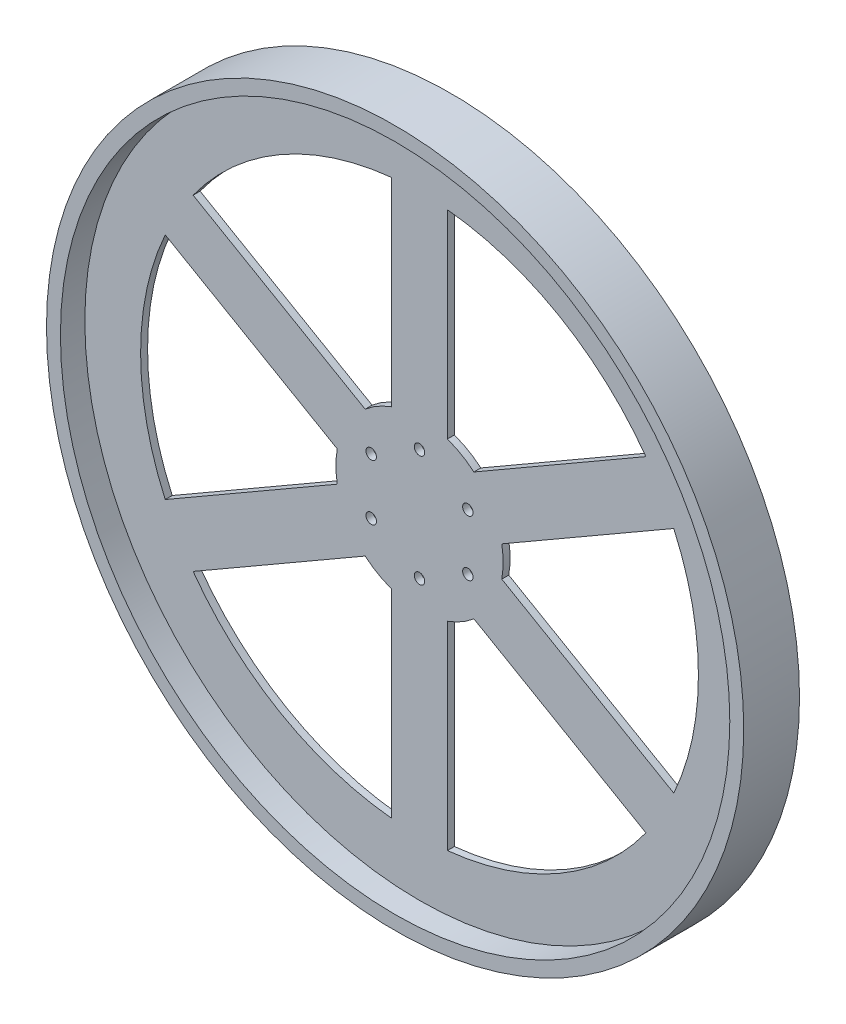
SolidWorks part; units mm, degrees
ref_plane "Front Plane" through (0, 0, 0) normal (0, 0, 1) x (1, 0, 0)
ref_plane "Top Plane" through (0, 0, 0) normal (0, 1, 0) x (1, 0, 0)
ref_plane "Right Plane" through (0, 0, 0) normal (1, 0, 0) x (0, 0, -1)
sketch "Sketch2" plane through (0, 0, 0) normal (0, 0, 1) x (1, 0, 0)
  line L0 (0, 0) -> (0, -254)
  line L1 (0, 0) -> (219.9705, -127)
  line L2 (97.2852, -85.497) -> (122.6852, -41.503) construction
  line L7 (-25.4, -127) -> (25.4, -127) construction
  line L8 (74.917, -13.924) -> (231.5678, -104.3664)
  line L13 (-25.4, -71.842) -> (-25.4, -252.7268)
  line L14 (49.517, -57.9181) -> (206.1678, -148.3604)
  line L15 (-25.4, -71.842) -> (-25.4, -252.7268)
  line L16 (25.4, -71.842) -> (25.4, -252.7268)
  line L17 (25.4, -71.842) -> (25.4, -252.7268)
  line L18 (-74.917, -13.924) -> (-231.5678, -104.3664)
  line L19 (-49.517, -57.9181) -> (-206.1678, -148.3604)
  line L20 (-49.517, 57.9181) -> (-206.1678, 148.3604)
  line L21 (-74.917, 13.924) -> (-231.5678, 104.3664)
  line L22 (25.4, 71.842) -> (25.4, 252.7268)
  line L23 (-25.4, 71.842) -> (-25.4, 252.7268)
  line L24 (74.917, 13.924) -> (231.5678, 104.3664)
  line L25 (49.517, 57.9181) -> (206.1678, 148.3604)
  circle A0 centre (0, 0) radius 304.8
  circle A3 centre (0, 0) radius 254
  circle A5 centre (0, 0) radius 254
  circle A7 centre (0, 0) radius 254
  circle A9 centre (0, 0) radius 254
  circle A11 centre (0, 0) radius 254
  circle A12 centre (0, 0) radius 76.2
  point P5 (0, -127)
  point P9 (109.9852, -63.5)
  point P12 (109.9852, -63.5)
  point P13 (0, -127)
  point P16 (122.6852, -41.503)
  point P20 (97.2852, -85.497)
  point P23 (25.4, -127)
  point P27 (-25.4, -127)
  point P50 (0, 0)
  point P54 (0, 0)
  dimension "D1" = 60
  dimension "D3" = 508
  dimension "D4" = 50.8
  dimension "D5" = 609.6
  dimension "D2" = 152.4
  dimension "D6" = 6
extrude "Boss-Extrude1" add sketch "Sketch2" along direction (0, 0, 1) on the side of the normal blind 3.175 and the other way blind 3.175 contours A12 L20 A3 L21 | A12 L22 A3 L23 | A12 L24 A3 L25 | A12 L0 L1 | L0 A12 L1 | A12 L18 A3 L19 | A12 L0 A3 L16 | A12 L13 A3 L0 | A12 L1 A3 L8 | A12 L14 A3 L1 | A0 A3 region at (24.2552, -42.0113, 0) region at (-4.851, 8.4023, 0) region at (12.7362, -164.1659, 0) region at (-12.7362, -164.1659, 0) region at (148.54, -71.0531, 0) region at (135.8038, -93.1128, 0) region at (-142.1719, -82.083, 0) region at (142.1719, 82.083, 0) region at (-142.1719, 82.083, 0) region at (0, 164.1659, 0) region at (-296.179, 0, 0)
sketch "Sketch5" plane through (0, 0, 0) normal (0, 0, 1) x (1, 0, 0)
  circle A0 centre (0, 0) radius 317.5
  circle A1 centre (0, 0) radius 304.8
extrude "Boss-Extrude2" add sketch "Sketch5" along normal blind 25.4 and the other way blind 25.4
sketch "Sketch6" plane through (0, 0, 3.175) normal (0, 0, 1) x (1, 0, 0)
  circle A2 centre (0, 50.8) radius 4.7625
  circle A3 centre (43.9941, 25.4) radius 4.7625
  circle A4 centre (43.9941, -25.4) radius 4.7625
  circle A5 centre (0, -50.8) radius 4.7625
  circle A6 centre (-43.9941, -25.4) radius 4.7625
  circle A7 centre (-43.9941, 25.4) radius 4.7625
  point P18 (0, 0)
  dimension "D1" = 6
extrude "Cut-Extrude4" cut sketch "Sketch6" against normal through all
